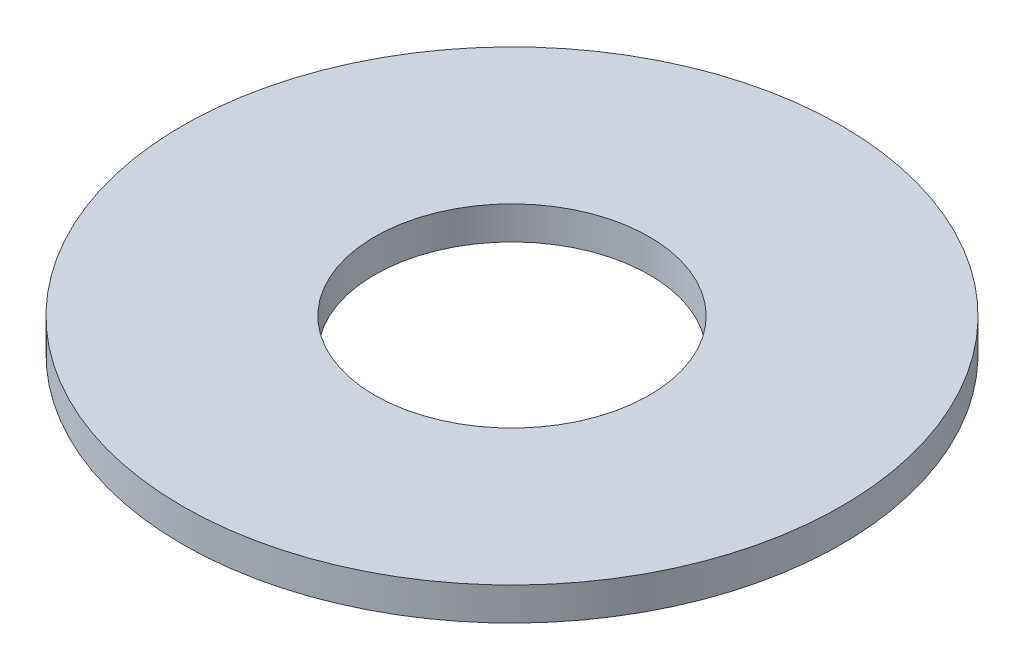
SolidWorks part; units mm, degrees
ref_plane "Front Plane" through (0, 0, 0) normal (0, 0, 1) x (1, 0, 0)
ref_plane "Top Plane" through (0, 0, 0) normal (0, 1, 0) x (1, 0, 0)
ref_plane "Right Plane" through (0, 0, 0) normal (1, 0, 0) x (0, 0, -1)
sketch "Sketch1" plane through (0, 0, 0) normal (0, 1, 0) x (1, 0, 0)
  circle A0 centre (0, 0) radius 90
  dimension "FLANGE_OD" = 180
extrude "Boss-Extrude1" add sketch "Sketch1" along normal blind 9
sketch "Sketch2" plane through (0, 0, 0) normal (0, 1, 0) x (1, 0, 0)
  circle A0 centre (0, 0) radius 37.5
  dimension "BORE_D" = 75
extrude "Cut-Extrude1" cut sketch "Sketch2" along normal through all
sketch "Sketch3" plane through (0, 9, 0) normal (0, 1, 0) x (1, 0, 0)
  circle A0 centre (0, 0) radius 29.1191 construction
  circle A1 centre (-29.1191, 0) radius 8.0577
  dimension "BOLT_D" = 16.1155
  dimension "BOLT_PCD" = 58.2382
extrude "Cut-Extrude2" cut sketch "Sketch3" against normal blind 5.5478 rebuild error yes
pattern_circular "CirPattern1" count 3 over 360 rebuild error yes
